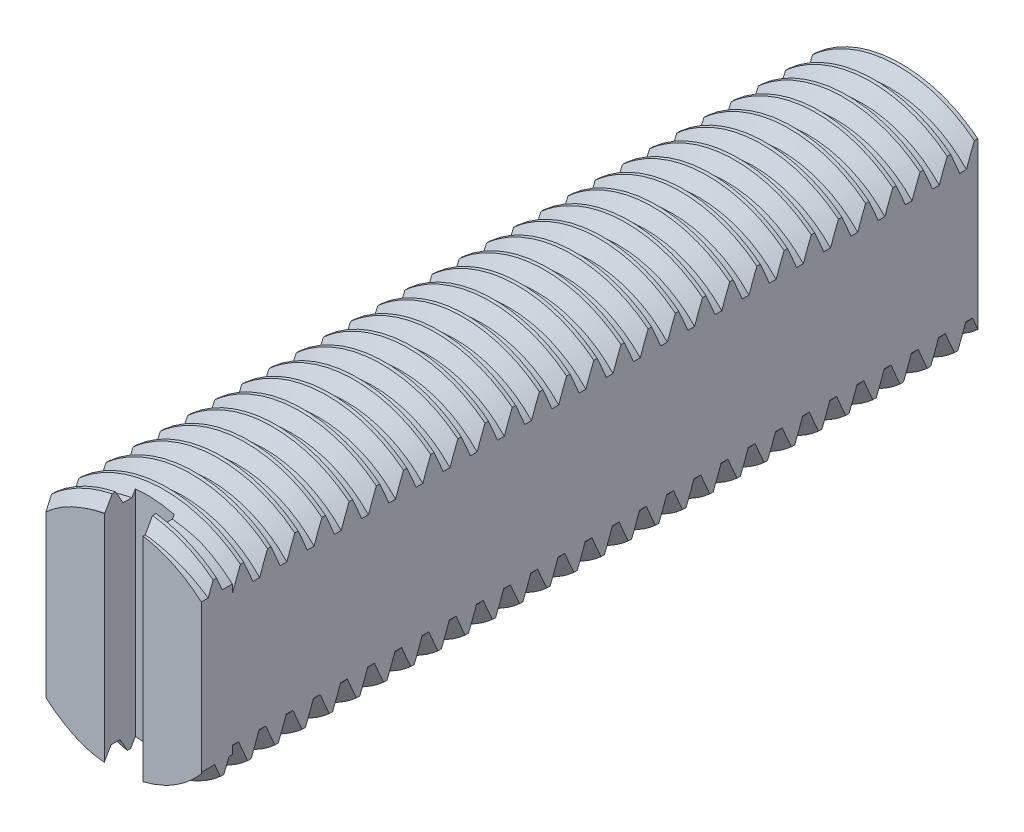
SolidWorks part; units mm, degrees
ref_plane "Front Plane" through (0, 0, 0) normal (0, 0, 1) x (1, 0, 0)
ref_plane "Top Plane" through (0, 0, 0) normal (0, 1, 0) x (1, 0, 0)
ref_plane "Right Plane" through (0, 0, 0) normal (1, 0, 0) x (0, 0, -1)
sketch "Sketch1" plane through (0, 0, 0) normal (0, 0, 1) x (1, 0, 0)
  circle A0 centre (0, 0) radius 15
  dimension "D1" = 30
extrude "Boss-Extrude1" add sketch "Sketch1" along normal blind 100
thread "Thread1" pitch 3.5 method cut profile "Thread Profile1" start angle 0, offset 3.5, length 110, pitch 3.5, diameter 30
ref_plane "Plane1" through (15, 0, -3.5) normal (0, -1, 0) x (1, 0, 0)
sketch "Thread Profile1" plane through (15, 0, -3.5) normal (0, -1, 0) x (1, 0, 0)
  line L0 (0, 0) -> (0, 3.5) construction
  line L11 (0, 0) -> (0, 3.0625)
  line L12 (0, 3.0625) -> (-1.8944, 1.9687)
  line L13 (-1.8944, 1.9687) -> (-1.8944, 1.0937)
  line L15 (-1.8944, 1.0937) -> (0, 0)
  line L17 (-1.8944, 1.5312) -> (0, 1.5312) construction
  point P2 (0, 0)
  dimension "Pitch" = 3.5
  dimension "Profile_Angle" = 60
  dimension "Profile_Land" = 0.875
  dimension "Profile_Height" = 1.8944
sketch "Sketch4" plane through (0, 0, 100) normal (0, 0, 1) x (1, 0, 0)
  line L0 (10, 15) -> (15, 15)
  line L1 (-10, -15) -> (10, -15) construction
  line L2 (-10, -15) -> (-10, 15)
  line L3 (-10, 15) -> (10, 15) construction
  line L4 (10, -15) -> (10, 15)
  line L5 (-10, -15) -> (10, 15) construction
  line L6 (-10, 15) -> (10, -15) construction
  line L7 (-15, -15) -> (15, -15) construction
  line L8 (-15, -15) -> (-15, 15)
  line L9 (-15, 15) -> (15, 15) construction
  line L10 (15, -15) -> (15, 15)
  line L11 (-15, -15) -> (15, 15) construction
  line L12 (-15, 15) -> (15, -15) construction
  line L13 (15, -15) -> (10, -15)
  line L14 (-10, -15) -> (-15, -15)
  line L15 (-10, 15) -> (-15, 15)
  point P0 (0, 0)
  point P6 (0, 0)
  dimension "D1" = 20
  dimension "D2" = 30
  dimension "D3" = 30
extrude "Cut-Extrude1" cut sketch "Sketch4" against normal blind 100
sketch "Sketch7" plane through (0, 0, 100) normal (0, 0, 1) x (1, 0, 0)
  line L2 (-10, -9.5) -> (-10, 9.5)
  line L3 (-10, -11.1803) -> (-10, 9.5555) construction
  line L4 (10, -9.5) -> (10, 9.5)
  line L5 (10, 8.4709) -> (10, -9.655) construction
  line L6 (-10, 9.5) -> (10, 9.5) construction
  line L7 (-10, -9.5) -> (10, -9.5) construction
  arc A2 (-10, 9.5) -> (10, 9.5) centre (0, -1.6803) cw
  arc A3 (-10, -9.5) -> (10, -9.5) centre (0, 1.6803) ccw
  point P6 (-10, 0)
  point P12 (10, 0)
  dimension "D2" = 15
  dimension "D3" = 15
  dimension "D1" = 19
extrude "Boss-Extrude2" add sketch "Sketch7" against normal blind 4
sketch "Sketch6" plane through (0, 0, 100) normal (0, 0, 1) x (1, 0, 0)
  line L1 (-2.5, -15) -> (2.5, -15)
  line L2 (-2.5, -15) -> (-2.5, 15)
  line L3 (-2.5, 15) -> (2.5, 15)
  line L4 (2.5, -15) -> (2.5, 15)
  line L5 (-2.5, -15) -> (2.5, 15) construction
  line L6 (-2.5, 15) -> (2.5, -15) construction
  arc A0 (-10, -11.1803) -> (-4.9431, -14.1621) centre (0, 0) ccw construction
  point P0 (0, 0)
  dimension "D1" = 5
extrude "Cut-Extrude3" cut sketch "Sketch6" against normal blind 4
